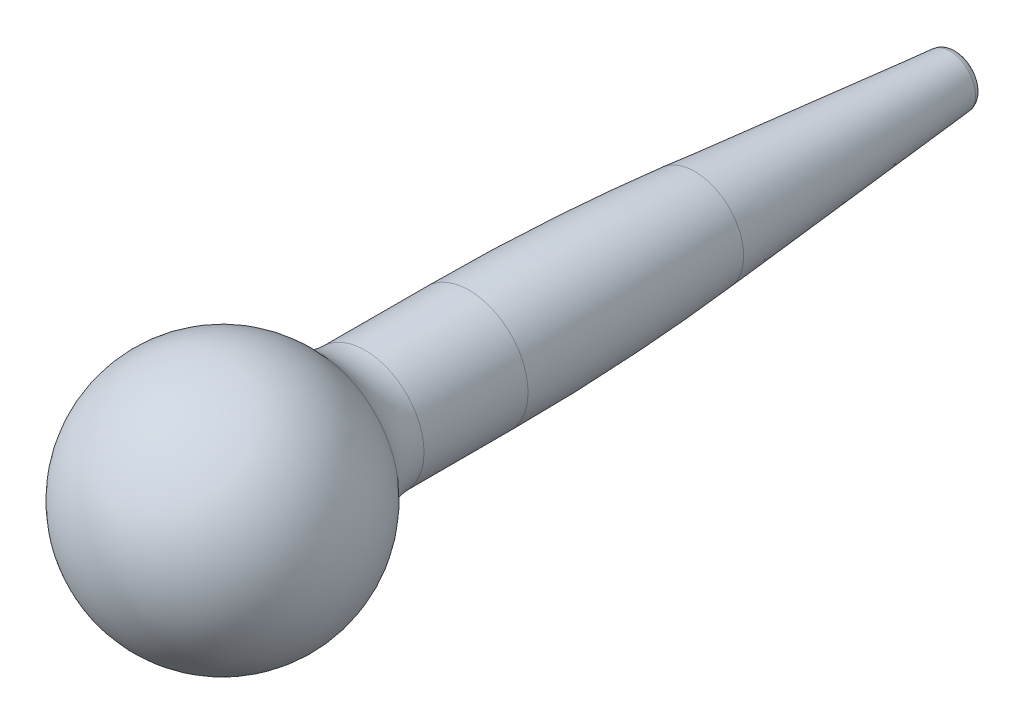
SolidWorks part; units mm, degrees
ref_plane "Front Plane" through (0, 0, 0) normal (0, 0, 1) x (1, 0, 0)
ref_plane "Top Plane" through (0, 0, 0) normal (0, 1, 0) x (1, 0, 0)
ref_plane "Right Plane" through (0, 0, 0) normal (1, 0, 0) x (0, 0, -1)
sketch "Sketch1" plane through (0, 0, 0) normal (0, 0, 1) x (1, 0, 0)
  circle A0 centre (0, 0) radius 6
  dimension "D1" = 12
extrude "Boss-Extrude1" add sketch "Sketch1" along normal blind 63.5
sketch "Sketch2" plane through (0, 0, 0) normal (1, 0, 0) x (0, 0, -1)
  line L0 (-63.5, 0) -> (-87.3933, 0)
  line L1 (-63.5, 6) -> (-63.5, -6) construction
  line L2 (-63.5, 6) -> (-63.5, 0)
  arc A1 (-87.3933, 0) -> (-63.5, 6) centre (-74.6933, 0) cw
  dimension "D1" = 12.7
revolve "Revolve1" add sketch "Sketch2" angle 360 about L0
sketch "Sketch3" plane through (0, 0, 0) normal (0, 0, -1) x (-1, 0, 0)
  line L1 (-0.7, 1.1) -> (0.7, 1.1)
  line L2 (-0.7, 1.1) -> (-0.7, -1.1)
  line L3 (-0.7, -1.1) -> (0.7, -1.1)
  line L4 (0.7, 1.1) -> (0.7, -1.1)
  point P2 (0.7, 0)
  point P5 (0, 1.1)
  dimension "D1" = 1.4
  dimension "D2" = 2.2
extrude "Cut-Extrude1" cut sketch "Sketch3" against normal blind 50.8
fillet "Fillet1" radius 6.35 1 edges at (6, 0, 63.5)
sketch "Sketch5" plane through (0, 0, 0) normal (0, 1, 0) x (1, 0, 0)
  line L0 (0, 0) -> (0, -38.1) construction
  line L1 (6, 0) -> (-6, 0) construction
  line L2 (0, -38.1) -> (-6, -38.1) construction
  line L3 (-6, 0) -> (-6, -60.1888) construction
  line L4 (-6, -38.1) -> (-2.54, 0)
  line L5 (-2.54, 0) -> (0, 0) construction
  line L6 (-6, -38.1) -> (-6, 0)
  line L7 (-6, 0) -> (-2.54, 0)
  dimension "D1" = 2.54
  dimension "D2" = 38.1
revolve "Cut-Revolve1" cut sketch "Sketch5" angle 360 about L0
fillet "Fillet2" radius 254 1 edges at (-6, 0, 38.1)
fillet "Fillet3" radius 0.762 1 edges at (-2.54, 0, 0)
